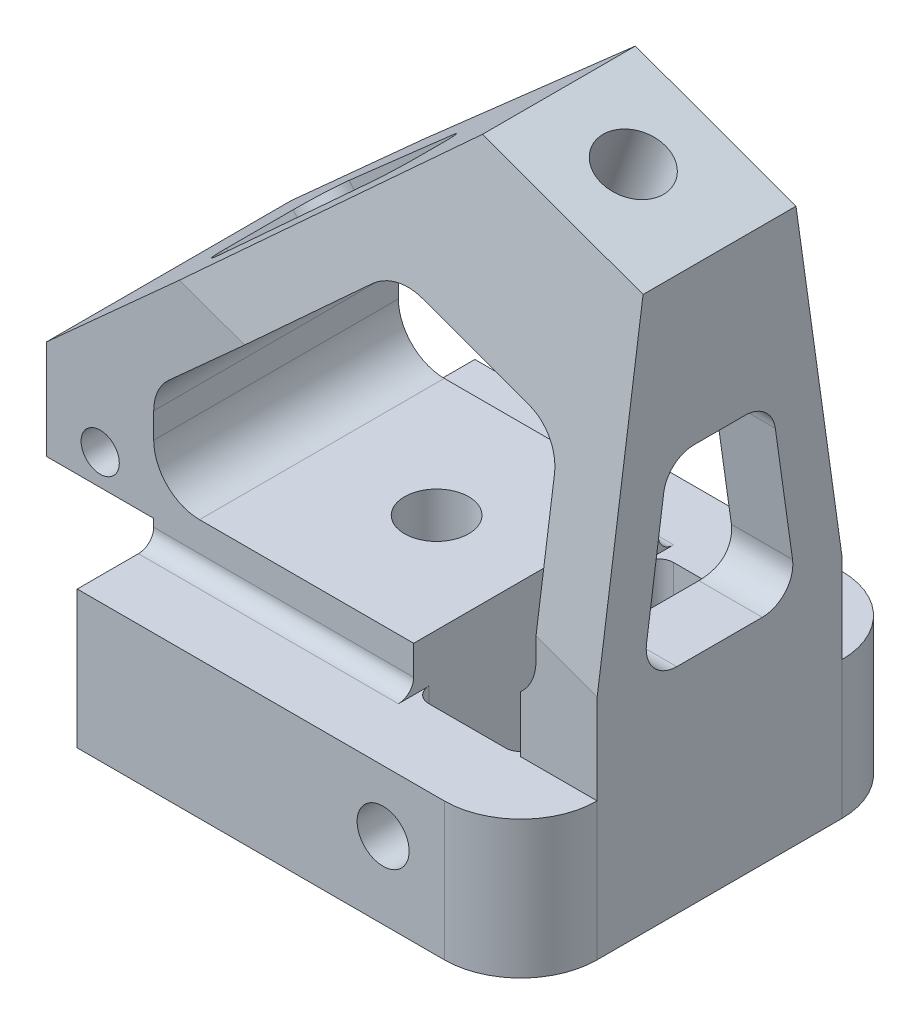
SolidWorks part; units mm, degrees
material "6061 Alloy"
ref_plane "Front Plane" through (0, 0, 0) normal (0, 0, 1) x (1, 0, 0)
ref_plane "Top Plane" through (0, 0, 0) normal (0, 1, 0) x (1, 0, 0)
ref_plane "Right Plane" through (0, 0, 0) normal (1, 0, 0) x (0, 0, -1)
sketch "Sketch1" plane through (0, 0, 0) normal (0, 0, 1) x (1, 0, 0)
  line L0 (0, 0) -> (36, 0)
  line L1 (36, 0) -> (36, 36.1783)
  line L2 (36, 36.1783) -> (25.5, 40)
  line L3 (25.5, 40) -> (0, 17)
  line L4 (0, 17) -> (0, 0)
  dimension "D2" = 17
  dimension "D3" = 40
  dimension "D4" = 36
  dimension "D5" = 25.5
  dimension "D6" = 20
extrude "Boss-Extrude1" add sketch "Sketch1" along normal mid plane 26
sketch "Sketch2" plane through (0, 0, 0) normal (-1, 0, 0) x (0, 0, 1)
  line L0 (13, 17) -> (13, 0) construction
  line L1 (-13, 0) -> (13, 0)
  line L2 (-13, 0) -> (-13, 9)
  line L3 (-13, 9) -> (13, 9)
  line L4 (13, 0) -> (13, 9)
  line L5 (13, 17) -> (-13, 17) construction
  dimension "D1" = 8
extrude "Cut-Extrude1" cut sketch "Sketch2" against normal blind 7
sketch "Sketch3" plane through (0, 0, 0) normal (-1, 0, 0) x (0, 0, 1)
  line L0 (13, 9) -> (-13, 9) construction
  line L1 (8, 9) -> (13.4602, 9)
  line L2 (8, 9) -> (8, 44.7276)
  line L3 (8, 44.7276) -> (13.4602, 44.7276)
  line L4 (13.4602, 9) -> (13.4602, 44.7276)
  line L5 (13, 17) -> (13, 9) construction
  line L6 (-8, 9) -> (-14.9908, 9)
  line L7 (-8, 9) -> (-8, 46.8043)
  line L8 (-8, 46.8043) -> (-14.9908, 46.8043)
  line L9 (-14.9908, 9) -> (-14.9908, 46.8043)
  dimension "D1" = 16
  dimension "D2" = 5
extrude "Cut-Extrude2" cut sketch "Sketch3" against normal through all
hole_wizard "M3x0.5 Tapped Hole2" positions "3DSketch1" profile "Sketch7" tap size "M3x0.5" standard "ANSI Metric"
sketch3d "3DSketch1"
  line L1 (7, 9, -8) -> (7, 9, -13) construction
  line L2 (7, 9, -13) -> (7, 0, -13) construction
  line L3 (7, 0, 13) -> (7, 9, 13) construction
  line L4 (7, 9, 13) -> (7, 9, 8) construction
  point P0 (7, 5, -9.5)
  point P2 (7, 5, 9.5)
  dimension "D1" = 4
  dimension "D2" = 3.5
  dimension "D3" = 3.5
  dimension "D4" = 4
sketch "Sketch7" plane through (7, 5, -9.5) normal (0, 1, 0) x (0, 0, 1)
  line L0 (0, 0) -> (0, 15.7511)
  line L1 (0, 15.7511) -> (1.25, 15)
  line L2 (1.25, 15) -> (1.25, 0)
  line L5 (1.25, 0) -> (0, 0)
  line L10 (0, 15.7511) -> (-1.25, 15) construction
  line L11 (0, -6.35) -> (0, 107.95) construction
  dimension "Tap Drill Dia." = 2.5
  dimension "Tap Drill Depth" = 15
  dimension "Drill Angle" = 118
cosmetic thread "Hole Thread2" parameters "D1"=12, "D2"=3
cosmetic thread "Hole Thread3" parameters "D1"=12, "D2"=3
hole_wizard "M3x0.5 Tapped Hole1" positions "3DSketch2" profile "Sketch8" tap size "M3x0.5" standard "ANSI Metric" end condition through all
sketch3d "3DSketch2"
  line L0 (7, 9, 8) -> (0, 9, 8) construction
  line L1 (0, 17, 8) -> (0, 9, 8) construction
  point P0 (3.5, 12.5, 8)
  dimension "D1" = 3.5
  dimension "D2" = 3.5
sketch "Sketch8" plane through (3.5, 12.5, 8) normal (1, 0, 0) x (0, -1, 0)
  line L0 (0, 0) -> (0, 21)
  line L1 (0, 21) -> (1.25, 21)
  line L2 (1.25, 21) -> (1.25, 0)
  line L5 (1.25, 0) -> (0, 0)
  line L11 (0, -6.35) -> (0, 107.95) construction
  dimension "Thru Tap Drill Dia." = 2.5
  dimension "Thru Tap Drill Depth" = 21
cosmetic thread "Hole Thread1" parameters "D2"=3
hole_wizard "M3 Clearance Hole1" positions "Sketch9" profile "Sketch10" hole size "M3" standard "ANSI Metric" end condition through all
sketch "Sketch9" plane through (0, 0, 13) normal (0, 0, 1) x (1, 0, 0)
  line L0 (7, 0) -> (36, 0) construction
  line L1 (7, 0) -> (7, 9) construction
  point P0 (27, 5)
  dimension "D1" = 5
  dimension "D2" = 20
sketch "Sketch10" plane through (27, 5, 13) normal (1, 0, 0) x (0, -1, 0)
  line L0 (0, 0) -> (0, 26)
  line L1 (0, 26) -> (1.7, 26)
  line L2 (1.7, 26) -> (1.7, 0)
  line L5 (1.7, 0) -> (0, 0)
  line L11 (0, -6.35) -> (0, 107.95) construction
  dimension "Thru Hole Dia." = 3.4
  dimension "Thru Hole Depth" = 26
ref_plane "Plane1" through (0, 17, 0) normal (0, -1, 0) x (-1, 0, 0)
sketch "Sketch13" plane through (0, 0, 8) normal (0, 0, 1) x (1, 0, 0)
  line L2 (32, 18.8712) -> (32, 26.9924)
  line L3 (32, 26.9924) -> (21.3488, 30.8691)
  line L4 (21.3488, 30.8691) -> (7, 17.927)
  line L5 (0, 17) -> (25.5, 40) construction
  line L6 (25.5, 40) -> (36, 36.1783) construction
  line L7 (36, 36.1783) -> (36, 9) construction
  line L8 (7, 17.927) -> (7, 11.927)
  line L9 (7, 11.927) -> (32, 11.927)
  line L10 (32, 11.927) -> (32, 18.8712)
  line L11 (0, 17) -> (0, 9) construction
  dimension "D1" = 4
  dimension "D2" = 10
  dimension "D3" = 4
  dimension "D4" = 7
  dimension "D5" = 6
extrude "Cut-Extrude3" cut sketch "Sketch13" against normal through all
fillet "Fillet2" radius 3 5 edges at (32, 26.9924, 0) (21.3488, 30.8691, 0) (32, 11.927, 0) (7, 11.927, 0) (7, 17.927, 0)
chamfer "Chamfer1" distance 20 distance2 3 2 edges at (30.75, 38.0892, 8) (30.75, 38.0892, -8) first distance on face at (19.8196, 20.1232, 8) first distance on face at (19.8196, 20.1232, -8)
sketch "Sketch14" plane through (36, 0, 0) normal (1, 0, 0) x (0, 0, -1)
  line L0 (-3.405, 26) -> (3.405, 26)
  line L1 (3.405, 26) -> (5.0965, 14)
  line L2 (5.0965, 14) -> (-5.0965, 14)
  line L3 (-5.0965, 14) -> (-3.405, 26)
  line L4 (-5, 36.1783) -> (-8, 14.8948) construction
  line L5 (8, 14.8948) -> (5, 36.1783) construction
  line L7 (-13, 0) -> (13, 0) construction
  dimension "D1" = 3
  dimension "D2" = 3
  dimension "D3" = 14
  dimension "D4" = 12
extrude "Cut-Extrude4" cut sketch "Sketch14" against normal up to next
fillet "Fillet3" radius 2 4 edges at (33.9266, 14, -5.0965) (33.9266, 14, 5.0965) (33.8939, 26, -3.405) (33.8939, 26, 3.405)
sketch "Sketch16" plane through (-8.455, 9.374, 0) normal (-0.6698, 0.7426, 0) x (0.7426, 0.6698, 0)
  line L0 (19.3861, 4.4552) -> (19.3861, -4.4552)
  line L1 (19.3861, -4.4552) -> (34.3861, -2.4676)
  line L2 (34.3861, -2.4676) -> (34.3861, 2.4676)
  line L3 (34.3861, 2.4676) -> (19.3861, 4.4552)
  line L4 (45.7263, 5) -> (23.0852, 8) construction
  line L5 (23.0852, -8) -> (45.7263, -5) construction
  line L6 (11.3861, -8) -> (11.3861, 8) construction
  dimension "D1" = 4
  dimension "D2" = 4
  dimension "D3" = 8
  dimension "D4" = 15
extrude "Cut-Extrude5" cut sketch "Sketch16" against normal up to next
fillet "Fillet4" radius 2 4 edges at (7.2801, 20.873, 4.4552) (7.2801, 20.873, -4.4552) (18.4186, 30.9195, 2.4676) (18.4186, 30.9195, -2.4676)
fillet "Fillet5" [suppressed] radius 2
hole_wizard "M5x0.8 Tapped Hole1" positions "Sketch17" profile "Sketch18" tap size "M5x0.8" standard "ANSI Metric" end condition up to next
sketch "Sketch17" plane through (0, 0, 0) normal (0, -1, 0) x (-1, 0, 0)
  line L0 (-7, -8) -> (-7, 8) construction
  line L1 (-7, 0) -> (-36, 0) construction
  line L2 (-7, 13) -> (-7, -13) construction
  line L3 (-36, -13) -> (-36, 13) construction
  point P0 (-17.5, 0)
  dimension "D1" = 10.5
sketch "Sketch18" plane through (17.5, 0, 0) normal (1, 0, 0) x (0, 0, -1)
  line L0 (0, 0) -> (0, 11.927)
  line L1 (0, 11.927) -> (2.1, 11.927)
  line L2 (2.1, 11.927) -> (2.1, 0)
  line L5 (2.1, 0) -> (0, 0)
  line L11 (0, -6.35) -> (0, 107.95) construction
  dimension "Thru Tap Drill Dia." = 4.2
  dimension "Thru Tap Drill Depth" = 11.927
cosmetic thread "Hole Thread4" parameters "D2"=5
fillet "Fillet6" radius 5 2 edges at (36, 4.5, 13) (36, 4.5, -13)
sketch "Sketch19" plane through (0, 0, 0) normal (0, -1, 0) x (1, 0, 0)
  line L0 (36, 8) -> (36, -8) construction
  line L1 (24, 8) -> (31, 8)
  line L2 (24, 8) -> (24, -8)
  line L3 (24, -8) -> (31, -8)
  line L4 (31, 8) -> (31, -8)
  line L5 (7, 13) -> (31, 13) construction
  dimension "D1" = 5
  dimension "D2" = 7
  dimension "D3" = 16
  dimension "D4" = 5
extrude "Cut-Extrude6" cut sketch "Sketch19" against normal up to next
fillet "Fillet7" radius 1 4 edges at (31, 4.5, -8) (24, 4.5, -8) (31, 4.5, 8) (24, 4.5, 8)
hole_wizard "M5x0.8 Tapped Hole2" positions "Sketch20" profile "Sketch21" tap size "M5x0.8" standard "ANSI Metric" end condition up to next
sketch "Sketch20" plane through (15.8387, 43.5164, 0) normal (0.342, 0.9397, 0) x (0.9397, -0.342, 0)
  line L2 (21.4552, 5) -> (10.2814, 5) construction
  line L3 (21.4552, -5) -> (21.4552, 5) construction
  point P0 (15.4552, 0)
  dimension "D1" = 6
  dimension "D2" = 5
sketch "Sketch21" plane through (30.3618, 38.2304, 0) normal (0, 0, 1) x (-0.9397, 0.342, 0)
  line L0 (0, 0) -> (0, 10)
  line L1 (0, 10) -> (2.675, 10)
  line L2 (2.1, 9.425) -> (2.1, 0)
  line L5 (2.1, 0) -> (0, 0)
  line L7 (2.675, 10) -> (2.1, 9.425)
  line L8 (-2.675, 10) -> (-2.1, 9.425) construction
  line L11 (0, -6.35) -> (0, 107.95) construction
  dimension "Thru Tap Drill Dia." = 4.2
  dimension "Thru Tap Drill Depth" = 10
  dimension "Far C'Sink Dia." = 5.35
  dimension "Far C'Sink Angle" = 90
cosmetic thread "Hole Thread5" parameters "D2"=5
chamfer "Chamfer2" distance 1.5 angle 45 2 edges at (3.5, 9, 8) (3.5, 9, -8)
fillet "Fillet8" radius 0.5 1 edges at (7, 9, 0)
fillet "Fillet9" radius 1 2 edges at (15.5, 9, -8) (15.5, 9, 8)
